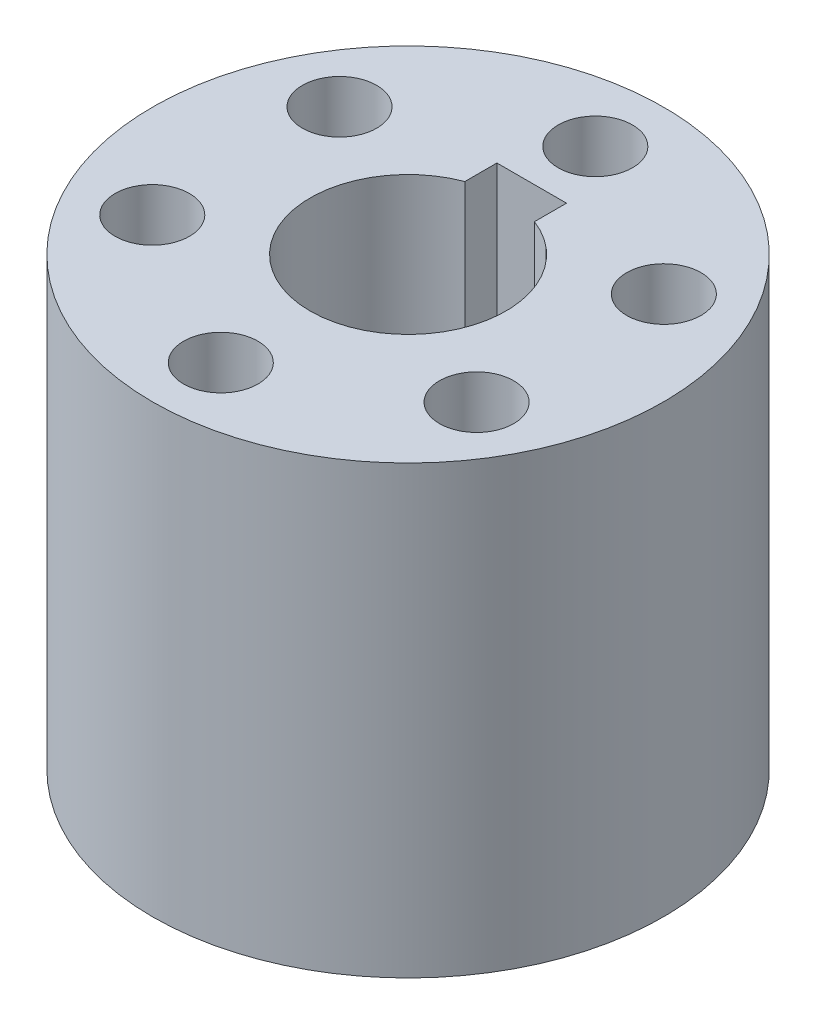
SolidWorks part; units mm, degrees
ref_plane "Front Plane" through (0, 0, 0) normal (0, 0, 1) x (1, 0, 0)
ref_plane "Top Plane" through (0, 0, 0) normal (0, 1, 0) x (1, 0, 0)
ref_plane "Right Plane" through (0, 0, 0) normal (1, 0, 0) x (0, 0, -1)
sketch "Sketch1" plane through (0, 0, 0) normal (0, 1, 0) x (1, 0, 0)
  circle A0 centre (0, 0) radius 18.9
extrude "Boss-Extrude1" add sketch "Sketch1" along normal blind 33
sketch "Sketch2" plane through (0, 33, 0) normal (0, 1, 0) x (1, 0, 0)
  line L1 (0, 13.8564) -> (-12, 6.9282)
  line L2 (-12, 6.9282) -> (-12, -6.9282)
  line L3 (-12, -6.9282) -> (0, -13.8564)
  line L4 (0, -13.8564) -> (12, -6.9282)
  line L5 (12, -6.9282) -> (12, 6.9282)
  line L6 (12, 6.9282) -> (0, 13.8564)
  circle A0 centre (0, 0) radius 12 construction
  circle A1 centre (0, 13.8564) radius 2.75
  circle A2 centre (12, 6.9282) radius 2.75
  circle A3 centre (12, -6.9282) radius 2.75
  circle A4 centre (0, -13.8564) radius 2.75
  circle A5 centre (-12, -6.9282) radius 2.75
  circle A6 centre (-12, 6.9282) radius 2.75
extrude "Cut-Extrude1" cut sketch "Sketch2" against normal blind 91.4 contours L1 A6 L2 | L2 A6 L1 | L6 A1 L1 | L1 A1 L6 | L5 A2 L6 | L6 A2 L5 | L4 A3 L5 | L5 A3 L4 | L3 A4 L4 | L4 A4 L3 | L2 A5 L3 | L3 A5 L2 region at (0, 33, -12.3403) region at (0, 33, -14.6145) region at (-10.687, 33, -6.1701) region at (-12.6565, 33, -7.3072) region at (12.6565, 33, -7.3072) region at (10.687, 33, -6.1701) region at (-10.687, 33, 6.1701) region at (-12.6565, 33, 7.3072) region at (12.6565, 33, 7.3072) region at (10.687, 33, 6.1701) region at (0, 33, 12.3403) region at (0, 33, 14.6145)
sketch "Sketch3" plane through (0, 33, 0) normal (0, 1, 0) x (1, 0, 0)
  line L0 (-2.575, 9.15) -> (2.575, 9.15)
  line L1 (-2.575, 9.15) -> (-2.575, 4)
  line L2 (-2.575, 4) -> (2.575, 4)
  line L3 (2.575, 9.15) -> (2.575, 4)
  circle A0 centre (0, 0) radius 7.25
  point P6 (0, 0)
  dimension "D1" = 5.15
  dimension "D2" = 5.15
  dimension "D3" = 9.15
  dimension "D4" = 2.575
extrude "Cut-Extrude2" cut sketch "Sketch3" against normal blind 86 contours L1 A0 L3 L2 | A0 L3 L0 L1 | L3 A0 L1 L2 region at (0, 33, -8.1175) region at (0, 33, -5.5505) region at (0, 33, 0.5929)
